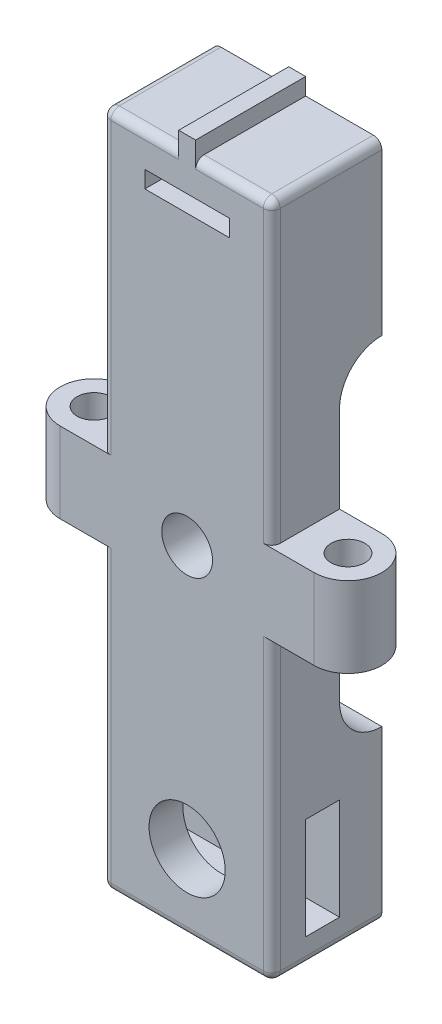
SolidWorks part; units mm, degrees
material "ABS"
ref_plane "Front Plane" through (0, 0, 0) normal (0, 0, 1) x (1, 0, 0)
ref_plane "Top Plane" through (0, 0, 0) normal (0, 1, 0) x (1, 0, 0)
ref_plane "Right Plane" through (0, 0, 0) normal (1, 0, 0) x (0, 0, -1)
sketch "Sketch1" plane through (0, 0, 0) normal (1, 0, 0) x (0, 0, -1)
  line L0 (0, -20) -> (0, 20)
  line L1 (0, 20) -> (5, 20)
  line L2 (5, 20) -> (5, 40)
  line L3 (5, 40) -> (-8, 40)
  line L4 (-8, 20) -> (-8, 40)
  line L5 (-8, 20) -> (-8, -20)
  line L6 (-8, 0) -> (0, 0) construction
  line L7 (-8, -40) -> (-8, -20)
  line L8 (5, -40) -> (-8, -40)
  line L9 (5, -20) -> (5, -40)
  line L10 (0, -20) -> (5, -20)
  dimension "D1" = 40
  dimension "D2" = 20
  dimension "D3" = 5
  dimension "D4" = 20
  dimension "D7" = 8
extrude "Boss-Extrude1" add sketch "Sketch1" along normal mid plane 20
sketch "Sketch7" plane through (0, 0, 0) normal (0, 1, 0) x (1, 0, 0)
  line L0 (0, 0) -> (0, -8) construction
  line L2 (10, -8) -> (-10, -8) construction
  line L3 (-15, 0) -> (-10, 0)
  line L4 (-15, -8) -> (-10, -8)
  line L5 (15, -8) -> (10, -8)
  line L6 (15, 0) -> (10, 0)
  line L7 (-10, 0) -> (-10, -8)
  line L8 (10, 0) -> (10, -8)
  circle A0 centre (-15, -4) radius 2
  arc A1 (15, 0) -> (15, -8) centre (15, -4) cw
  arc A2 (-15, 0) -> (-15, -8) centre (-15, -4) ccw
  circle A3 centre (15, -4) radius 2
  dimension "D1" = 4
  dimension "D4" = 8
  dimension "D2" = 15
extrude "Boss-Extrude4" add sketch "Sketch7" along normal mid plane 9.5
sketch "Sketch8" plane through (0, 0, 0) normal (0, 0, -1) x (-1, 0, 0)
  circle A0 centre (0, 0) radius 3
  dimension "D1" = 6
extrude "Cut-Extrude1" cut sketch "Sketch8" against normal up to surface (8 mm away) up to face at (-0.8333, 5.875, 8)
fillet "Fillet1" radius 1 10 edges at (-10, -40, 1.5) (10, -40, 1.5) (-10, 40, 1.5) (10, 40, 1.5) (0, -40, 8) (0, 40, 8)
sketch "Sketch9" plane through (0, 0, -5) normal (0, 0, -1) x (-1, 0, 0)
  point P0 (0, -31)
  dimension "D1" = 31
hole_wizard "M8 Clearance Hole1" positions "3DSketch2" profile "Sketch13" hole size "M8" standard "ANSI Metric" end condition through all
sketch3d "3DSketch2"
  point P0 (0, -31, -5)
sketch "Sketch13" plane through (0, -31, -5) normal (1, 0, 0) x (0, 1, 0)
  line L0 (0, 0) -> (0, 13)
  line L1 (0, 13) -> (4.5, 13)
  line L2 (4.5, 13) -> (4.5, 0)
  line L5 (4.5, 0) -> (0, 0)
  line L11 (0, -6.35) -> (0, 107.95) construction
  dimension "Thru Hole Dia." = 9
  dimension "Thru Hole Depth" = 13
fillet "Fillet2" radius 5 2 edges at (0, 20, 0) (0, -20, 0)
sketch "Sketch15" plane through (-10, 0, 0) normal (-1, 0, 0) x (0, 0, 1)
  line L0 (8, -39) -> (8, -4.75) construction
  line L1 (4, -25) -> (0, -25)
  line L2 (4, -25) -> (4, -37)
  line L3 (4, -37) -> (0, -37)
  line L4 (0, -25) -> (0, -37)
  line L5 (4, -25) -> (0, -37) construction
  line L6 (4, -37) -> (0, -25) construction
  point P0 (2, -31)
  dimension "D1" = 4
  dimension "D2" = 12
  dimension "D3" = 4
extrude "Cut-Extrude2" cut sketch "Sketch15" against normal up to surface (20 mm away) up to face at (10, -21.4434, 0.2559)
sketch "Sketch16" plane through (0, 0, 8) normal (0, 0, 1) x (1, 0, 0)
  line L1 (5, 36) -> (-5, 36)
  line L2 (5, 36) -> (5, 34)
  line L3 (5, 34) -> (-5, 34)
  line L4 (-5, 36) -> (-5, 34)
  line L5 (5, 36) -> (-5, 34) construction
  line L6 (5, 34) -> (-5, 36) construction
  point P0 (0, 35)
  dimension "D1" = 10
  dimension "D2" = 2
  dimension "D3" = 35
extrude "Cut-Extrude3" cut sketch "Sketch16" against normal through all
fillet "Fillet3" radius 5 1 edges at (0, 34, -5)
sketch "Sketch17" plane through (0, 40, 0) normal (0, 1, 0) x (1, 0, 0)
  line L0 (9, -8) -> (-9, -8) construction
  line L1 (1, 5) -> (-1, 5)
  line L2 (1, 5) -> (1, -8)
  line L3 (1, -8) -> (-1, -8)
  line L4 (-1, 5) -> (-1, -8)
  line L5 (1, 5) -> (-1, -8) construction
  line L6 (1, -8) -> (-1, 5) construction
  line L7 (9, 5) -> (-9, 5) construction
  point P0 (0, -1.5)
  dimension "D1" = 2
extrude "Boss-Extrude5" add sketch "Sketch17" along normal blind 2 and the other way up to body (2 mm away)
